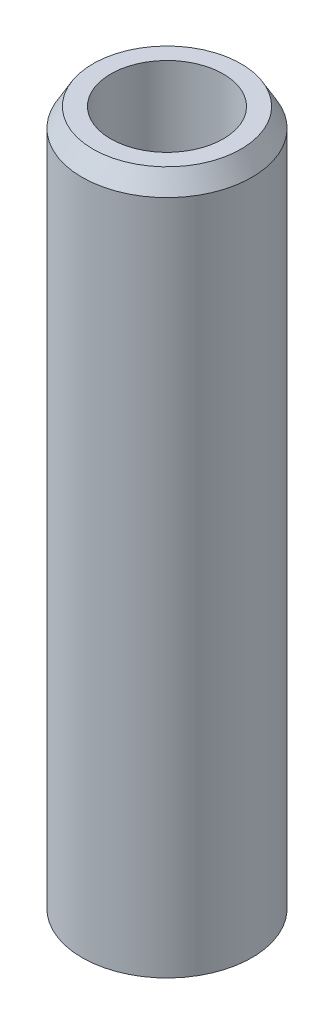
SolidWorks part; units mm, degrees
ref_plane "Front Plane" through (0, 0, 0) normal (0, 0, 1) x (1, 0, 0)
ref_plane "Top Plane" through (0, 0, 0) normal (0, 1, 0) x (1, 0, 0)
ref_plane "Right Plane" through (0, 0, 0) normal (1, 0, 0) x (0, 0, -1)
sketch "Sketch1" plane through (0, 0, 0) normal (0, 1, 0) x (1, 0, 0)
  circle A0 centre (0, 0) radius 22.5
  dimension "SHAFT_OD" = 45
extrude "Boss-Extrude1" add sketch "Sketch1" along normal blind 186.9302
sketch "Sketch2" plane through (0, 0, 0) normal (0, 1, 0) x (1, 0, 0)
  circle A0 centre (0, 0) radius 14.9092
  dimension "BORE_D" = 29.8184
extrude "Cut-Extrude1" cut sketch "Sketch2" along normal through all
chamfer "Chamfer1" distance 5.0181 angle 30 2 edges at (0, 186.9302, 22.5) (0, 0, 22.5) first distance on face at (0, 186.9302, 22.5) first distance on face at (0, 0, 14.9092)
